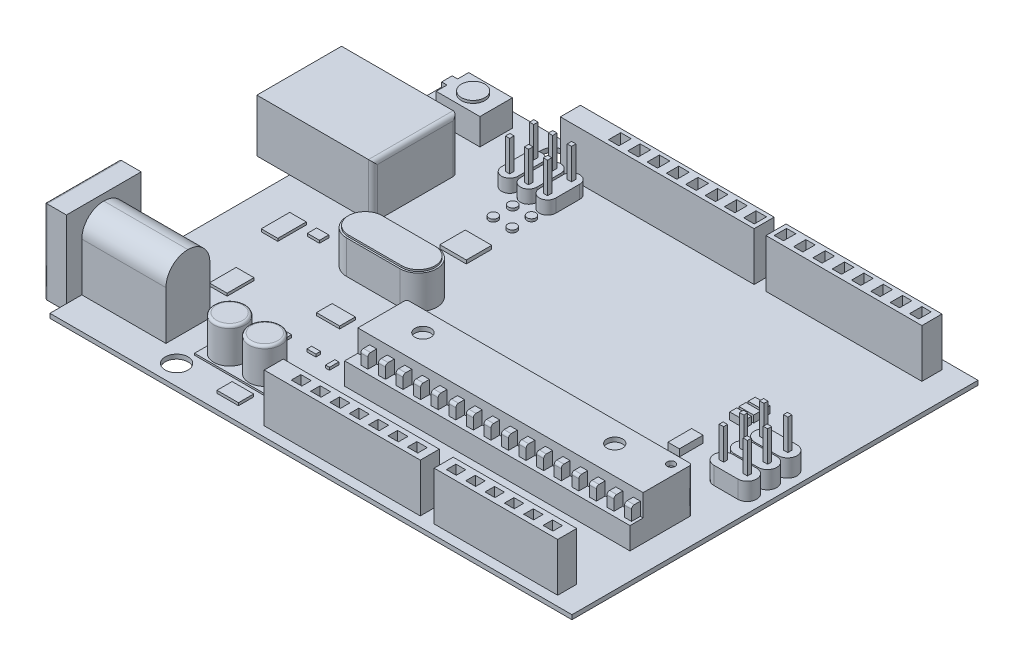
SolidWorks part; units mm, degrees
ref_plane "Front Plane" through (0, 0, 0) normal (0, 0, 1) x (1, 0, 0)
ref_plane "Top Plane" through (0, 0, 0) normal (0, 1, 0) x (1, 0, 0)
ref_plane "Right Plane" through (0, 0, 0) normal (1, 0, 0) x (0, 0, -1)
sketch "Sketch1" plane through (0, 0, 0) normal (0, 1, 0) x (1, 0, 0)
  line L0 (99, 231) -> (495, 231) construction
ref_plane "Plane1" through (0, 100, 0) normal (0, 1, 0) x (1, 0, 0)
sketch "Sketch2" plane through (0, 100, 0) normal (0, 1, 0) x (1, 0, 0)
  line L0 (406.2485, 32.6469) -> (410.391, 32.6469)
  line L1 (232.8531, 32.6469) -> (406.2485, 32.6469)
  line L2 (232.8531, 32.6469) -> (232.8531, 11.0076)
  line L3 (232.8531, 11.0076) -> (406.2485, 11.0076)
  line L5 (410.391, 32.6469) -> (410.391, 11.0076)
  line L6 (410.391, 11.0076) -> (406.2485, 11.0076)
extrude "Boss-Extrude2" add sketch "Sketch2" along normal blind 55
sketch "Sketch3" plane through (0, 100, 0) normal (0, 1, 0) x (1, 0, 0)
  line L0 (410.391, 32.6469) -> (232.8531, 32.6469) construction
  line L1 (426.2106, 32.6469) -> (566.7256, 32.6469)
  line L2 (426.2106, 32.6469) -> (426.2106, 11.0076)
  line L3 (426.2106, 11.0076) -> (566.7256, 11.0076)
  line L4 (566.7256, 32.6469) -> (566.7256, 11.0076)
  line L5 (232.8531, 11.0076) -> (410.391, 11.0076) construction
extrude "Boss-Extrude3" add sketch "Sketch3" along normal blind 55 separate body
sketch "Sketch4" plane through (0, 100, 0) normal (0, 1, 0) x (1, 0, 0)
  line L0 (258.1323, 27.3712) -> (269.983, 27.3712)
  line L5 (269.983, 27.3712) -> (269.983, 16.5363)
  line L6 (269.983, 16.5363) -> (258.1323, 16.5363)
  line L7 (258.1323, 16.5363) -> (258.1323, 27.3712)
  line L8 (280.1323, 16.5363) -> (280.1323, 27.3712)
  line L9 (280.1323, 27.3712) -> (291.983, 27.3712)
  line L10 (291.983, 16.5363) -> (280.1323, 16.5363)
  line L11 (291.983, 27.3712) -> (291.983, 16.5363)
  line L12 (302.1323, 16.5363) -> (302.1323, 27.3712)
  line L13 (302.1323, 27.3712) -> (313.983, 27.3712)
  line L14 (313.983, 16.5363) -> (302.1323, 16.5363)
  line L15 (313.983, 27.3712) -> (313.983, 16.5363)
  line L16 (324.1323, 16.5363) -> (324.1323, 27.3712)
  line L17 (324.1323, 27.3712) -> (335.983, 27.3712)
  line L18 (335.983, 16.5363) -> (324.1323, 16.5363)
  line L19 (335.983, 27.3712) -> (335.983, 16.5363)
  line L20 (346.1323, 16.5363) -> (346.1323, 27.3712)
  line L21 (346.1323, 27.3712) -> (357.983, 27.3712)
  line L22 (357.983, 16.5363) -> (346.1323, 16.5363)
  line L23 (357.983, 27.3712) -> (357.983, 16.5363)
  line L24 (368.1323, 16.5363) -> (368.1323, 27.3712)
  line L25 (368.1323, 27.3712) -> (379.983, 27.3712)
  line L26 (379.983, 16.5363) -> (368.1323, 16.5363)
  line L27 (379.983, 27.3712) -> (379.983, 16.5363)
  line L28 (390.1323, 16.5363) -> (390.1323, 27.3712)
  line L29 (390.1323, 27.3712) -> (401.983, 27.3712)
  line L30 (401.983, 16.5363) -> (390.1323, 16.5363)
  line L31 (401.983, 27.3712) -> (401.983, 16.5363)
  line L32 (434.5905, 27.3712) -> (445.7945, 27.3712)
  line L33 (445.7945, 27.3712) -> (445.7945, 16.5363)
  line L34 (445.7945, 16.5363) -> (434.5905, 16.5363)
  line L35 (434.5905, 16.5363) -> (434.5905, 27.3712)
  line L36 (456.5905, 16.5363) -> (456.5905, 27.3712)
  line L37 (456.5905, 27.3712) -> (467.7945, 27.3712)
  line L38 (467.7945, 27.3712) -> (467.7945, 16.5363)
  line L39 (467.7945, 16.5363) -> (456.5905, 16.5363)
  line L40 (478.5905, 16.5363) -> (478.5905, 27.3712)
  line L41 (478.5905, 27.3712) -> (489.7945, 27.3712)
  line L42 (489.7945, 27.3712) -> (489.7945, 16.5363)
  line L43 (489.7945, 16.5363) -> (478.5905, 16.5363)
  line L44 (500.5905, 16.5363) -> (500.5905, 27.3712)
  line L45 (500.5905, 27.3712) -> (511.7945, 27.3712)
  line L46 (511.7945, 27.3712) -> (511.7945, 16.5363)
  line L47 (511.7945, 16.5363) -> (500.5905, 16.5363)
  line L48 (522.5905, 16.5363) -> (522.5905, 27.3712)
  line L49 (522.5905, 27.3712) -> (533.7945, 27.3712)
  line L50 (533.7945, 27.3712) -> (533.7945, 16.5363)
  line L51 (533.7945, 16.5363) -> (522.5905, 16.5363)
  line L52 (544.5905, 16.5363) -> (544.5905, 27.3712)
  line L53 (544.5905, 27.3712) -> (555.7945, 27.3712)
  line L54 (555.7945, 27.3712) -> (555.7945, 16.5363)
  line L55 (555.7945, 16.5363) -> (544.5905, 16.5363)
  dimension "D1" = 7
  dimension "D2" = 6
extrude "Cut-Extrude1" cut sketch "Sketch4" along normal blind 50 from offset 5
sketch "Sketch5" plane through (0, 100, 0) normal (0, 1, 0) x (1, 0, 0)
  line L1 (151.8134, 451.812) -> (372.2687, 451.812)
  line L2 (151.8134, 451.812) -> (151.8134, 428.9817)
  line L3 (151.8134, 428.9817) -> (372.2687, 428.9817)
  line L4 (372.2687, 451.812) -> (372.2687, 428.9817)
extrude "Boss-Extrude4" add sketch "Sketch5" along normal blind 55 separate body
sketch "Sketch6" plane through (0, 100, 0) normal (0, 1, 0) x (1, 0, 0)
  line L0 (372.2687, 451.812) -> (151.8134, 451.812) construction
  line L1 (385.742, 451.812) -> (563.1714, 451.812)
  line L2 (385.742, 451.812) -> (385.742, 428.9817)
  line L3 (385.742, 428.9817) -> (563.1714, 428.9817)
  line L4 (563.1714, 451.812) -> (563.1714, 428.9817)
  line L5 (151.8134, 428.9817) -> (372.2687, 428.9817) construction
extrude "Boss-Extrude5" add sketch "Sketch6" along normal blind 55 separate body
sketch "Sketch7" plane through (0, 100, 0) normal (0, 1, 0) x (1, 0, 0)
  line L0 (201.7231, 447.7471) -> (213.6594, 447.7471)
  line L1 (213.6594, 447.7471) -> (213.6594, 433.7449)
  line L2 (213.6594, 433.7449) -> (201.7231, 433.7449)
  line L3 (201.7231, 433.7449) -> (201.7231, 447.7471)
  line L4 (223.7231, 433.7449) -> (223.7231, 447.7471)
  line L5 (235.6594, 447.7471) -> (235.6594, 433.7449)
  line L6 (235.6594, 433.7449) -> (223.7231, 433.7449)
  line L7 (223.7231, 447.7471) -> (235.6594, 447.7471)
  line L8 (245.7231, 433.7449) -> (245.7231, 447.7471)
  line L9 (257.6594, 447.7471) -> (257.6594, 433.7449)
  line L10 (257.6594, 433.7449) -> (245.7231, 433.7449)
  line L11 (245.7231, 447.7471) -> (257.6594, 447.7471)
  line L12 (267.7231, 433.7449) -> (267.7231, 447.7471)
  line L13 (279.6594, 447.7471) -> (279.6594, 433.7449)
  line L14 (279.6594, 433.7449) -> (267.7231, 433.7449)
  line L15 (267.7231, 447.7471) -> (279.6594, 447.7471)
  line L16 (289.7231, 433.7449) -> (289.7231, 447.7471)
  line L17 (301.6594, 447.7471) -> (301.6594, 433.7449)
  line L18 (301.6594, 433.7449) -> (289.7231, 433.7449)
  line L19 (289.7231, 447.7471) -> (301.6594, 447.7471)
  line L20 (311.7231, 433.7449) -> (311.7231, 447.7471)
  line L21 (323.6594, 447.7471) -> (323.6594, 433.7449)
  line L22 (323.6594, 433.7449) -> (311.7231, 433.7449)
  line L23 (311.7231, 447.7471) -> (323.6594, 447.7471)
  line L24 (333.7231, 433.7449) -> (333.7231, 447.7471)
  line L25 (345.6594, 447.7471) -> (345.6594, 433.7449)
  line L26 (345.6594, 433.7449) -> (333.7231, 433.7449)
  line L27 (333.7231, 447.7471) -> (345.6594, 447.7471)
  line L28 (355.7231, 433.7449) -> (355.7231, 447.7471)
  line L29 (367.6594, 447.7471) -> (367.6594, 433.7449)
  line L30 (367.6594, 433.7449) -> (355.7231, 433.7449)
  line L31 (355.7231, 447.7471) -> (367.6594, 447.7471)
  line L32 (390.4075, 447.7471) -> (400.9504, 447.7471)
  line L33 (400.9504, 447.7471) -> (400.9504, 433.7449)
  line L34 (400.9504, 433.7449) -> (390.4075, 433.7449)
  line L35 (390.4075, 433.7449) -> (390.4075, 447.7471)
  line L36 (412.4075, 433.7449) -> (412.4075, 447.7471)
  line L37 (412.4075, 447.7471) -> (422.9504, 447.7471)
  line L38 (422.9504, 447.7471) -> (422.9504, 433.7449)
  line L39 (422.9504, 433.7449) -> (412.4075, 433.7449)
  line L40 (434.4075, 433.7449) -> (434.4075, 447.7471)
  line L41 (434.4075, 447.7471) -> (444.9504, 447.7471)
  line L42 (444.9504, 447.7471) -> (444.9504, 433.7449)
  line L43 (444.9504, 433.7449) -> (434.4075, 433.7449)
  line L44 (456.4075, 433.7449) -> (456.4075, 447.7471)
  line L45 (456.4075, 447.7471) -> (466.9504, 447.7471)
  line L46 (466.9504, 447.7471) -> (466.9504, 433.7449)
  line L47 (466.9504, 433.7449) -> (456.4075, 433.7449)
  line L48 (478.4075, 433.7449) -> (478.4075, 447.7471)
  line L49 (478.4075, 447.7471) -> (488.9504, 447.7471)
  line L50 (488.9504, 447.7471) -> (488.9504, 433.7449)
  line L51 (488.9504, 433.7449) -> (478.4075, 433.7449)
  line L52 (500.4075, 433.7449) -> (500.4075, 447.7471)
  line L53 (500.4075, 447.7471) -> (510.9504, 447.7471)
  line L54 (510.9504, 447.7471) -> (510.9504, 433.7449)
  line L55 (510.9504, 433.7449) -> (500.4075, 433.7449)
  line L56 (522.4075, 433.7449) -> (522.4075, 447.7471)
  line L57 (522.4075, 447.7471) -> (532.9504, 447.7471)
  line L58 (532.9504, 447.7471) -> (532.9504, 433.7449)
  line L59 (532.9504, 433.7449) -> (522.4075, 433.7449)
  line L60 (544.4075, 433.7449) -> (544.4075, 447.7471)
  line L61 (544.4075, 447.7471) -> (554.9504, 447.7471)
  line L62 (554.9504, 447.7471) -> (554.9504, 433.7449)
  line L63 (554.9504, 433.7449) -> (544.4075, 433.7449)
  dimension "D1" = 8
  dimension "D2" = 8
extrude "Cut-Extrude2" cut sketch "Sketch7" along normal blind 50 from offset 5
sketch "Sketch8" plane through (0, 100, 0) normal (0, 1, 0) x (1, 0, 0)
  line L1 (239.5675, 166.433) -> (564.1861, 166.433)
  line L2 (239.5675, 166.433) -> (239.5675, 95.8017)
  line L3 (239.5675, 95.8017) -> (564.1861, 95.8017)
  line L4 (564.1861, 166.433) -> (564.1861, 95.8017)
extrude "Boss-Extrude6" add sketch "Sketch8" along normal blind 25 separate body
sketch "Sketch9" plane through (0, 125, 0) normal (0, 1, 0) x (1, 0, 0)
  line L0 (564.1861, 95.8017) -> (564.1861, 166.433) construction
  line L1 (239.5675, 166.433) -> (564.1861, 166.433)
  line L2 (239.5675, 166.433) -> (239.5675, 110.8017)
  line L3 (239.5675, 110.8017) -> (564.1861, 110.8017)
  line L4 (564.1861, 166.433) -> (564.1861, 110.8017)
  line L5 (239.5675, 95.8017) -> (564.1861, 95.8017) construction
  dimension "D1" = 15
extrude "Boss-Extrude7" add sketch "Sketch9" along normal blind 25
fillet "Fillet1" radius 3 1 edges at (239.5675, 125, -166.433)
fillet "Fillet2" radius 3 1 edges at (564.1861, 125, -166.433)
sketch "Sketch10" plane through (0, 0, -110.8017) normal (0, 0, 1) x (1, 0, 0)
  line L0 (239.5675, 125) -> (564.1861, 125) construction
  line L1 (253.0094, 140) -> (261.0094, 140)
  line L2 (253.0094, 140) -> (253.0094, 125)
  line L3 (253.0094, 125) -> (261.0094, 125)
  line L4 (261.0094, 140) -> (261.0094, 125)
  dimension "D1" = 15
  dimension "D2" = 8
extrude "Boss-Extrude8" add sketch "Sketch10" along normal blind 10
fillet "Fillet3" radius 3 1 edges at (257.0094, 140, -100.8017)
pattern_linear "LPattern1" count 16 spacing 20 along (1, 0, 0) of "Boss-Extrude8", "Fillet3"
sketch "Sketch11" plane through (0, 150, 0) normal (0, 1, 0) x (1, 0, 0)
  circle A0 centre (281.3729, 143.0171) radius 9
  circle A1 centre (499.6617, 143.0171) radius 9
  circle A2 centre (552.0412, 154.8066) radius 4.5132
  dimension "D1" = 18
  dimension "D2" = 18
extrude "Cut-Extrude3" cut sketch "Sketch11" against normal blind 5
sketch "Sketch12" plane through (0, 100, 0) normal (0, 1, 0) x (1, 0, 0)
  line L0 (547.5175, 264.7495) -> (574.6286, 264.7495) construction
  line L1 (547.5175, 275.4513) -> (574.6286, 275.4513)
  line L2 (547.5175, 254.0478) -> (574.6286, 254.0478)
  line L3 (547.5175, 241.7495) -> (574.6286, 241.7495) construction
  line L4 (547.5175, 252.4513) -> (574.6286, 252.4513)
  line L5 (547.5175, 231.0478) -> (574.6286, 231.0478)
  line L6 (547.5175, 218.7495) -> (574.6286, 218.7495) construction
  line L7 (547.5175, 229.4513) -> (574.6286, 229.4513)
  line L8 (547.5175, 208.0478) -> (574.6286, 208.0478)
  arc A0 (547.5175, 275.4513) -> (547.5175, 254.0478) centre (547.5175, 264.7495) ccw
  arc A1 (574.6286, 254.0478) -> (574.6286, 275.4513) centre (574.6286, 264.7495) ccw
  arc A2 (547.5175, 252.4513) -> (547.5175, 231.0478) centre (547.5175, 241.7495) ccw
  arc A3 (574.6286, 231.0478) -> (574.6286, 252.4513) centre (574.6286, 241.7495) ccw
  arc A4 (547.5175, 229.4513) -> (547.5175, 208.0478) centre (547.5175, 218.7495) ccw
  arc A5 (574.6286, 208.0478) -> (574.6286, 229.4513) centre (574.6286, 218.7495) ccw
  point P2 (561.0731, 264.7495)
  point P10 (561.0731, 241.7495)
  point P17 (561.0731, 218.7495)
  dimension "D1" = 3
extrude "Boss-Extrude9" add sketch "Sketch12" along normal blind 20 separate body
sketch "Sketch13" plane through (0, 120, 0) normal (0, 1, 0) x (1, 0, 0)
  line L0 (545.0175, 243.9932) -> (550.0175, 243.9932)
  line L1 (545.0175, 266.9932) -> (550.0175, 266.9932)
  line L2 (545.0175, 266.9932) -> (545.0175, 262.5059)
  line L3 (545.0175, 262.5059) -> (550.0175, 262.5059)
  line L4 (550.0175, 266.9932) -> (550.0175, 262.5059)
  line L5 (545.0175, 266.9932) -> (550.0175, 262.5059) construction
  line L6 (545.0175, 262.5059) -> (550.0175, 266.9932) construction
  line L7 (572.1286, 266.9932) -> (577.1286, 266.9932)
  line L8 (572.1286, 266.9932) -> (572.1286, 262.5059)
  line L9 (572.1286, 262.5059) -> (577.1286, 262.5059)
  line L10 (577.1286, 266.9932) -> (577.1286, 262.5059)
  line L11 (572.1286, 266.9932) -> (577.1286, 262.5059) construction
  line L12 (572.1286, 262.5059) -> (577.1286, 266.9932) construction
  line L13 (545.0175, 243.9932) -> (545.0175, 239.5059)
  line L14 (545.0175, 239.5059) -> (550.0175, 239.5059)
  line L15 (550.0175, 243.9932) -> (550.0175, 239.5059)
  line L16 (572.1286, 243.9932) -> (572.1286, 239.5059)
  line L17 (572.1286, 243.9932) -> (577.1286, 243.9932)
  line L18 (572.1286, 239.5059) -> (577.1286, 239.5059)
  line L19 (577.1286, 243.9932) -> (577.1286, 239.5059)
  line L20 (545.0175, 220.9932) -> (550.0175, 220.9932)
  line L21 (545.0175, 220.9932) -> (545.0175, 216.5059)
  line L22 (545.0175, 216.5059) -> (550.0175, 216.5059)
  line L23 (550.0175, 220.9932) -> (550.0175, 216.5059)
  line L24 (572.1286, 220.9932) -> (572.1286, 216.5059)
  line L25 (572.1286, 220.9932) -> (577.1286, 220.9932)
  line L26 (572.1286, 216.5059) -> (577.1286, 216.5059)
  line L27 (577.1286, 220.9932) -> (577.1286, 216.5059)
  point P0 (547.5175, 264.7495)
  point P6 (574.6286, 264.7495)
  dimension "D1" = 5
  dimension "D2" = 5
  dimension "D3" = 3
extrude "Boss-Extrude10" add sketch "Sketch13" along normal blind 35
sketch "Sketch14" plane through (0, 100, 0) normal (0, 1, 0) x (1, 0, 0)
  line L1 (486.6022, 243.5044) -> (499.6563, 243.5044)
  line L2 (486.6022, 243.5044) -> (486.6022, 216.5804)
  line L3 (486.6022, 216.5804) -> (499.6563, 216.5804)
  line L4 (499.6563, 243.5044) -> (499.6563, 216.5804)
  line L5 (486.6022, 243.5044) -> (499.6563, 216.5804) construction
  line L6 (486.6022, 216.5804) -> (499.6563, 243.5044) construction
  point P0 (493.1293, 230.0424)
extrude "Boss-Extrude11" add sketch "Sketch14" along normal blind 8 separate body
sketch "Sketch15" plane through (0, 100, 0) normal (0, 1, 0) x (1, 0, 0)
  line L1 (491.9055, 310.6026) -> (508.631, 310.6026)
  line L2 (491.9055, 310.6026) -> (491.9055, 302.6026)
  line L3 (491.9055, 302.6026) -> (508.631, 302.6026)
  line L4 (508.631, 310.6026) -> (508.631, 302.6026)
  line L5 (491.9055, 300.1026) -> (508.631, 300.1026)
  line L6 (491.9055, 300.1026) -> (491.9055, 292.1026)
  line L7 (491.9055, 292.1026) -> (508.631, 292.1026)
  line L8 (508.631, 300.1026) -> (508.631, 292.1026)
  line L9 (491.9055, 289.6026) -> (508.631, 289.6026)
  line L10 (491.9055, 289.6026) -> (491.9055, 281.6026)
  line L11 (491.9055, 281.6026) -> (508.631, 281.6026)
  line L12 (508.631, 289.6026) -> (508.631, 281.6026)
  dimension "D1" = 8
  dimension "D2" = 8
  dimension "D3" = 8
  dimension "D4" = 2.5
  dimension "D5" = 2.5
extrude "Boss-Extrude12" add sketch "Sketch15" along normal blind 8 separate body
sketch "Sketch16" plane through (0, 100, 0) normal (0, 1, 0) x (1, 0, 0)
  line L0 (136.8418, 413.6852) -> (136.8418, 386.3944) construction
  line L1 (146.172, 413.6852) -> (146.172, 386.3944)
  line L2 (127.5116, 413.6852) -> (127.5116, 386.3944)
  line L3 (158.3418, 413.6852) -> (158.3418, 386.3944) construction
  line L4 (167.672, 413.6852) -> (167.672, 386.3944)
  line L5 (149.0116, 413.6852) -> (149.0116, 386.3944)
  line L6 (179.8418, 413.6852) -> (179.8418, 386.3944) construction
  line L7 (189.172, 413.6852) -> (189.172, 386.3944)
  line L8 (170.5116, 413.6852) -> (170.5116, 386.3944)
  arc A0 (146.172, 413.6852) -> (127.5116, 413.6852) centre (136.8418, 413.6852) ccw
  arc A1 (127.5116, 386.3944) -> (146.172, 386.3944) centre (136.8418, 386.3944) ccw
  arc A2 (167.672, 413.6852) -> (149.0116, 413.6852) centre (158.3418, 413.6852) ccw
  arc A3 (149.0116, 386.3944) -> (167.672, 386.3944) centre (158.3418, 386.3944) ccw
  arc A4 (189.172, 413.6852) -> (170.5116, 413.6852) centre (179.8418, 413.6852) ccw
  arc A5 (170.5116, 386.3944) -> (189.172, 386.3944) centre (179.8418, 386.3944) ccw
  point P2 (136.8418, 400.0398)
  point P10 (158.3418, 400.0398)
  point P17 (179.8418, 400.0398)
  dimension "D1" = 3
extrude "Boss-Extrude13" add sketch "Sketch16" along normal blind 15 separate body
sketch "Sketch17" plane through (0, 115, 0) normal (0, 1, 0) x (1, 0, 0)
  line L0 (155.9448, 388.8944) -> (160.7388, 388.8944)
  line L1 (134.4448, 416.1852) -> (139.2388, 416.1852)
  line L2 (134.4448, 416.1852) -> (134.4448, 411.1852)
  line L3 (134.4448, 411.1852) -> (139.2388, 411.1852)
  line L4 (139.2388, 416.1852) -> (139.2388, 411.1852)
  line L5 (134.4448, 416.1852) -> (139.2388, 411.1852) construction
  line L6 (134.4448, 411.1852) -> (139.2388, 416.1852) construction
  line L7 (134.4448, 388.8944) -> (139.2388, 388.8944)
  line L8 (134.4448, 388.8944) -> (134.4448, 383.8944)
  line L9 (134.4448, 383.8944) -> (139.2388, 383.8944)
  line L10 (139.2388, 388.8944) -> (139.2388, 383.8944)
  line L11 (134.4448, 388.8944) -> (139.2388, 383.8944) construction
  line L12 (134.4448, 383.8944) -> (139.2388, 388.8944) construction
  line L13 (155.9448, 388.8944) -> (155.9448, 383.8944)
  line L14 (155.9448, 383.8944) -> (160.7388, 383.8944)
  line L15 (160.7388, 388.8944) -> (160.7388, 383.8944)
  line L16 (155.9448, 411.1852) -> (160.7388, 411.1852)
  line L17 (155.9448, 416.1852) -> (160.7388, 416.1852)
  line L18 (160.7388, 416.1852) -> (160.7388, 411.1852)
  line L19 (155.9448, 416.1852) -> (155.9448, 411.1852)
  line L20 (177.4448, 388.8944) -> (182.2388, 388.8944)
  line L21 (177.4448, 388.8944) -> (177.4448, 383.8944)
  line L22 (177.4448, 383.8944) -> (182.2388, 383.8944)
  line L23 (182.2388, 388.8944) -> (182.2388, 383.8944)
  line L24 (177.4448, 411.1852) -> (182.2388, 411.1852)
  line L25 (177.4448, 416.1852) -> (182.2388, 416.1852)
  line L26 (182.2388, 416.1852) -> (182.2388, 411.1852)
  line L27 (177.4448, 416.1852) -> (177.4448, 411.1852)
  point P0 (136.8418, 413.6852)
  point P6 (136.8418, 386.3944)
  dimension "D1" = 5
  dimension "D2" = 5
  dimension "D3" = 3
extrude "Boss-Extrude14" add sketch "Sketch17" along normal blind 35
sketch "Sketch18" plane through (0, 100, 0) normal (0, 1, 0) x (1, 0, 0)
  circle A0 centre (159.0143, 367.571) radius 5
  circle A1 centre (180.3105, 367.571) radius 5
  dimension "D1" = 10
  dimension "D2" = 10
extrude "Boss-Extrude15" add sketch "Sketch18" along normal blind 3 separate body
sketch "Sketch19" plane through (0, 100, 0) normal (0, 1, 0) x (1, 0, 0)
  circle A0 centre (158.9108, 345.6157) radius 5
  circle A1 centre (180.4006, 345.6157) radius 5
  dimension "D1" = 10
  dimension "D2" = 10
extrude "Boss-Extrude16" add sketch "Sketch19" along normal blind 3 separate body
sketch "Sketch20" plane through (0, 100, 0) normal (0, 1, 0) x (1, 0, 0)
  line L1 (158.2506, 314.3814) -> (188.3208, 314.3814)
  line L2 (158.2506, 314.3814) -> (158.2506, 285.4353)
  line L3 (158.2506, 285.4353) -> (188.3208, 285.4353)
  line L4 (188.3208, 314.3814) -> (188.3208, 285.4353)
extrude "Boss-Extrude17" add sketch "Sketch20" along normal blind 4 separate body
sketch "Sketch21" plane through (0, 100, 0) normal (0, 1, 0) x (1, 0, 0)
  line L0 (132.6768, 226.138) -> (193.0983, 226.138) construction
  line L1 (132.6768, 247.2153) -> (193.0983, 247.2153)
  line L2 (132.6768, 205.0608) -> (193.0983, 205.0608)
  arc A0 (132.6768, 247.2153) -> (132.6768, 205.0608) centre (132.6768, 226.138) ccw
  arc A1 (193.0983, 205.0608) -> (193.0983, 247.2153) centre (193.0983, 226.138) ccw
  point P2 (162.8876, 226.138)
extrude "Boss-Extrude18" add sketch "Sketch21" along normal blind 38 separate body
sketch "Sketch22" plane through (0, 138, 0) normal (0, 1, 0) x (1, 0, 0)
  line L4 (132.6768, 207.0608) -> (193.0983, 207.0608)
  line L5 (193.0983, 245.2153) -> (132.6768, 245.2153)
  line L6 (132.6768, 207.0608) -> (193.0983, 207.0608)
  line L7 (193.0983, 245.2153) -> (132.6768, 245.2153)
  arc A4 (132.6768, 245.2153) -> (132.6768, 207.0608) centre (132.6768, 226.138) ccw
  arc A5 (193.0983, 207.0608) -> (193.0983, 245.2153) centre (193.0983, 226.138) ccw
  arc A6 (132.6768, 245.2153) -> (132.6768, 207.0608) centre (132.6768, 226.138) ccw
  arc A7 (193.0983, 207.0608) -> (193.0983, 245.2153) centre (193.0983, 226.138) ccw
  dimension "D1" = 2
extrude "Boss-Extrude19" add sketch "Sketch22" along normal blind 2
sketch "Sketch23" plane through (0, 100, 0) normal (0, 1, 0) x (1, 0, 0)
  line L1 (153.9538, 167.1464) -> (180.3513, 167.1464)
  line L2 (153.9538, 167.1464) -> (153.9538, 149.3102)
  line L3 (153.9538, 149.3102) -> (180.3513, 149.3102)
  line L4 (180.3513, 167.1464) -> (180.3513, 149.3102)
extrude "Boss-Extrude20" add sketch "Sketch23" along normal blind 3 separate body
sketch "Sketch24" plane through (0, 100, 0) normal (0, 1, 0) x (1, 0, 0)
  line L1 (153.1434, 113.4833) -> (161.5743, 113.4833)
  line L2 (153.1434, 113.4833) -> (153.1434, 102.8042)
  line L3 (153.1434, 102.8042) -> (161.5743, 102.8042)
  line L4 (161.5743, 113.4833) -> (161.5743, 102.8042)
  line L5 (184.3377, 113.4833) -> (194.4548, 113.4833)
  line L6 (184.3377, 113.4833) -> (184.3377, 108.1437)
  line L7 (184.3377, 108.1437) -> (194.4548, 108.1437)
  line L8 (194.4548, 113.4833) -> (194.4548, 108.1437)
  line L9 (210.7545, 113.4833) -> (215.251, 113.4833)
  line L10 (210.7545, 113.4833) -> (210.7545, 102.8042)
  line L11 (210.7545, 102.8042) -> (215.251, 102.8042)
  line L12 (215.251, 113.4833) -> (215.251, 102.8042)
extrude "Boss-Extrude21" add sketch "Sketch24" along normal blind 3 separate body
sketch "Sketch25" plane through (0, 100, 0) normal (0, 1, 0) x (1, 0, 0)
  line L1 (123.6278, 80.8259) -> (203.6278, 80.8259)
  line L2 (123.6278, 80.8259) -> (123.6278, 40.9226)
  line L3 (123.6278, 40.9226) -> (203.6278, 40.9226)
  line L4 (203.6278, 80.8259) -> (203.6278, 40.9226)
  dimension "D1" = 80
extrude "Boss-Extrude22" add sketch "Sketch25" along normal blind 2 separate body
sketch "Sketch26" plane through (0, 102, 0) normal (0, 1, 0) x (1, 0, 0)
  line L0 (203.6278, 40.9226) -> (203.6278, 80.8259) construction
  line L1 (123.6278, 80.8259) -> (123.6278, 40.9226) construction
  circle A0 centre (143.6278, 60.8743) radius 18
  circle A1 centre (183.6278, 60.8743) radius 18
  dimension "D1" = 36
  dimension "D2" = 36
  dimension "D3" = 20
  dimension "D4" = 20
extrude "Boss-Extrude23" add sketch "Sketch26" along normal blind 40
fillet "Fillet4" radius 3 2 edges at (143.6278, 142, -42.8743) (183.6278, 142, -42.8743)
sketch "Sketch27" plane through (0, 100, 0) normal (0, 1, 0) x (1, 0, 0)
  line L1 (173.8923, 33.417) -> (198.3841, 33.417)
  line L2 (173.8923, 33.417) -> (173.8923, 16.1562)
  line L3 (173.8923, 16.1562) -> (198.3841, 16.1562)
  line L4 (198.3841, 33.417) -> (198.3841, 16.1562)
extrude "Boss-Extrude24" add sketch "Sketch27" along normal blind 3 separate body
sketch "Sketch28" plane through (0, 100, 0) normal (0, 1, 0) x (1, 0, 0)
  line L1 (-37.2502, 369.0521) -> (94.7376, 369.0521)
  line L2 (-37.2502, 369.0521) -> (-37.2502, 272.7367)
  line L3 (-37.2502, 272.7367) -> (94.7376, 272.7367)
  line L4 (94.7376, 369.0521) -> (94.7376, 272.7367)
extrude "Boss-Extrude25" add sketch "Sketch28" along normal blind 60 separate body
sketch "Sketch29" plane through (-37.2502, 0, 0) normal (-1, 0, 0) x (0, 0, 1)
  line L6 (-359.0521, 143.6242) -> (-341.0521, 150.1652)
  line L7 (-341.0521, 150.1652) -> (-300.7367, 150.1652)
  line L8 (-300.7367, 150.1652) -> (-282.7367, 143.6242)
  line L9 (-282.7367, 110) -> (-282.7367, 160)
  line L10 (-359.0521, 110) -> (-282.7367, 110)
  line L11 (-359.0521, 160) -> (-359.0521, 110)
  line L12 (-282.7367, 110) -> (-282.7367, 143.6242)
  line L13 (-359.0521, 110) -> (-282.7367, 110)
  line L14 (-359.0521, 143.6242) -> (-359.0521, 110)
  dimension "D2" = 18
  dimension "D3" = 18
  dimension "D1" = 10
extrude "Cut-Extrude4" cut sketch "Sketch29" against normal blind 80
sketch "Sketch30" plane through (42.7498, 0, 0) normal (-1, 0, 0) x (0, 0, 1)
  line L1 (-342.958, 136.3049) -> (-302.9442, 136.3049)
  line L2 (-342.958, 136.3049) -> (-342.958, 121.8855)
  line L3 (-342.958, 121.8855) -> (-302.9442, 121.8855)
  line L4 (-302.9442, 136.3049) -> (-302.9442, 121.8855)
  line L5 (-342.958, 136.3049) -> (-302.9442, 121.8855) construction
  line L6 (-342.958, 121.8855) -> (-302.9442, 136.3049) construction
  point P0 (-322.9511, 129.0952)
extrude "Boss-Extrude26" add sketch "Sketch30" along normal blind 80
fillet "Fillet5" radius 5 5 edges at (94.7376, 160, -320.8944) (94.7376, 130, -369.0521) (94.7376, 130, -272.7367) (-37.2502, 126.8121, -359.0521) (-37.2502, 126.8121, -282.7367)
sketch "Sketch31" plane through (0, 100, 0) normal (0, 1, 0) x (1, 0, 0)
  line L0 (31.0074, 445.4587) -> (80.7545, 445.4587)
  line L1 (80.7545, 445.4587) -> (80.7545, 408.5177)
  line L2 (80.7545, 408.5177) -> (31.0074, 408.5177)
  line L3 (31.0074, 408.5177) -> (31.0074, 420.8314)
  line L4 (31.0074, 420.8314) -> (24.8506, 420.8314)
  line L5 (24.8506, 420.8314) -> (24.8506, 432.8987)
  line L6 (24.8506, 432.8987) -> (31.0074, 432.8987)
  line L7 (31.0074, 432.8987) -> (31.0074, 445.4587)
extrude "Boss-Extrude27" add sketch "Sketch31" along normal blind 30 separate body
sketch "Sketch32" plane through (0, 130, 0) normal (0, 1, 0) x (1, 0, 0)
  circle A0 centre (54.5785, 426.9882) radius 13.3549
extrude "Boss-Extrude28" add sketch "Sketch32" along normal blind 3
sketch "Sketch33" plane through (0, 100, 0) normal (0, 1, 0) x (1, 0, 0)
  line L1 (0, 36.281) -> (95.7081, 36.281)
  line L2 (0, 36.281) -> (0, 86.281)
  line L3 (0, 86.281) -> (95.7081, 86.281)
  line L4 (95.7081, 36.281) -> (95.7081, 86.281)
  dimension "D1" = 50
extrude "Boss-Extrude29" add sketch "Sketch33" along normal blind 80 separate body
sketch "Sketch34" plane through (0, 0, 0) normal (-1, 0, 0) x (0, 0, 1)
  line L0 (-86.281, 140) -> (-36.281, 140) construction
  line L1 (-86.281, 180) -> (-86.281, 100) construction
  line L2 (-36.281, 180) -> (-36.281, 100) construction
  line L4 (-103.781, 187.5) -> (-18.781, 187.5)
  line L5 (-103.781, 187.5) -> (-103.781, 92.5)
  line L6 (-103.781, 92.5) -> (-18.781, 92.5)
  line L7 (-18.781, 187.5) -> (-18.781, 92.5)
  line L8 (-103.781, 187.5) -> (-18.781, 92.5) construction
  line L9 (-103.781, 92.5) -> (-18.781, 187.5) construction
  point P6 (-61.281, 140)
  dimension "D1" = 85
  dimension "D2" = 95
extrude "Boss-Extrude30" add sketch "Sketch34" along normal blind 25
fillet "Fillet6" radius 25 2 edges at (47.854, 180, -86.281) (47.854, 180, -36.281)
sketch "Sketch35" plane through (-25, 0, 0) normal (-1, 0, 0) x (0, 0, 1)
  circle A0 centre (-61.281, 139.1841) radius 21.698
extrude "Cut-Extrude5" cut sketch "Sketch35" against normal blind 97
fillet "Fillet7" radius 3 4 edges at (-25, 92.5, -61.281) (-25, 140, -103.781) (-25, 140, -18.781) (-25, 187.5, -61.281)
sketch "Sketch36" plane through (0, 100, 0) normal (0, 1, 0) x (1, 0, 0)
  line L1 (39.9665, 232.8832) -> (58.7981, 232.8832)
  line L2 (39.9665, 232.8832) -> (39.9665, 200.4928)
  line L3 (39.9665, 200.4928) -> (58.7981, 200.4928)
  line L4 (58.7981, 232.8832) -> (58.7981, 200.4928)
  line L5 (70.6334, 232.8832) -> (84.4161, 232.8832)
  line L6 (70.6334, 232.8832) -> (70.6334, 222.2829)
  line L7 (70.6334, 222.2829) -> (84.4161, 222.2829)
  line L8 (84.4161, 232.8832) -> (84.4161, 222.2829)
extrude "Boss-Extrude31" add sketch "Sketch36" along normal blind 3 separate body
sketch "Sketch37" plane through (0, 100, 0) normal (0, 1, 0) x (1, 0, 0)
  line L1 (63.7421, 148.2013) -> (83.9854, 148.2013)
  line L2 (63.7421, 148.2013) -> (63.7421, 117.6211)
  line L3 (63.7421, 117.6211) -> (83.9854, 117.6211)
  line L4 (83.9854, 148.2013) -> (83.9854, 117.6211)
extrude "Boss-Extrude32" add sketch "Sketch37" along normal blind 3 separate body
sketch "Sketch39" plane through (0, 100, 0) normal (0, 1, 0) x (1, 0, 0)
  line L1 (0, 0) -> (594, 0)
  line L2 (0, 0) -> (0, 462)
  line L3 (0, 462) -> (594, 462)
  line L4 (594, 0) -> (594, 462)
  dimension "D1" = 594
  dimension "D2" = 462
extrude "Boss-Extrude33" add sketch "Sketch39" against normal blind 5
sketch "Sketch38" plane through (0, 100, 0) normal (0, 1, 0) x (1, 0, 0)
  circle A0 centre (132.4115, 439.8756) radius 13.537
  circle A1 centre (121.4771, 22.6691) radius 12.9867
extrude "Cut-Extrude6" cut sketch "Sketch38" against normal through all
scale "Scale1" scale about centroid uniform scaling yes scale factor 0.5
